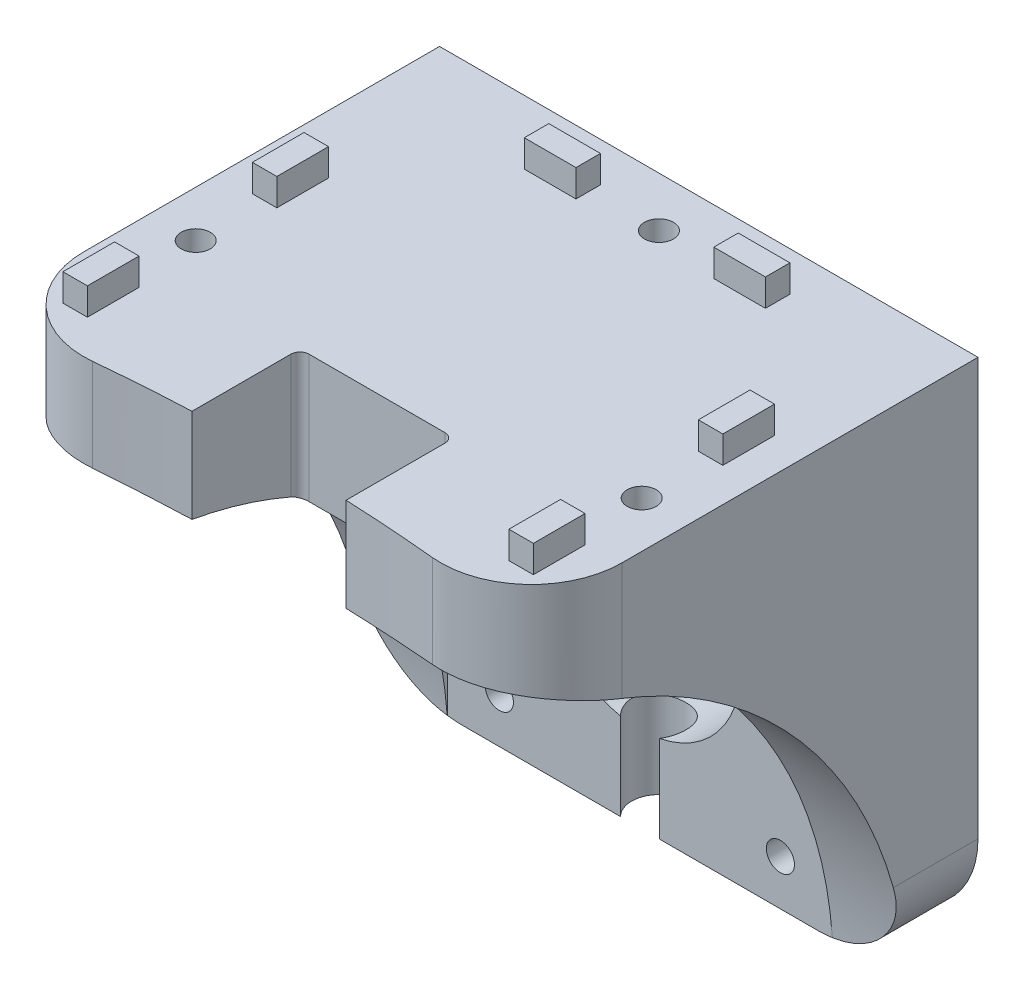
SolidWorks part; units mm, degrees
ref_plane "Alzado" through (0, 0, 0) normal (0, 0, 1) x (1, 0, 0)
ref_plane "Planta" through (0, 0, 0) normal (0, 1, 0) x (1, 0, 0)
ref_plane "Vista lateral" through (0, 0, 0) normal (1, 0, 0) x (0, 0, -1)
sketch "Croquis1" plane through (0, 0, 0) normal (0, 1, 0) x (1, 0, 0)
  line L1 (0, 0) -> (59.4, 0)
  line L2 (0, 0) -> (0, 48.6)
  line L3 (0, 48.6) -> (59.4, 48.6)
  line L4 (59.4, 0) -> (59.4, 48.6)
  dimension "D1" = 59.4
  dimension "D2" = 48.6
extrude "Saliente-Extruir1" add sketch "Croquis1" along normal blind 56
sketch "Croquis2" plane through (0, 56, 0) normal (0, 1, 0) x (1, 0, 0)
  line L1 (5.1, 48.6) -> (5.1, 0) construction
  line L2 (59.4, 48.6) -> (0, 48.6) construction
  line L3 (0, 0) -> (59.4, 0) construction
  line L4 (0, 45.1) -> (59.4, 45.1) construction
  line L5 (0, 48.6) -> (0, 0) construction
  line L6 (59.4, 0) -> (59.4, 48.6) construction
  line L7 (29.7, 48.6) -> (29.7, 0) construction
  line L8 (43.1, 46.35) -> (43.1, 43.45)
  line L9 (22.2, 46.35) -> (16.3, 46.35)
  line L10 (22.2, 46.35) -> (22.2, 43.45)
  line L11 (22.2, 43.45) -> (16.3, 43.45)
  line L12 (16.3, 46.35) -> (16.3, 43.45)
  line L13 (37.2, 43.45) -> (43.1, 43.45)
  line L14 (37.2, 46.35) -> (37.2, 43.45)
  line L15 (37.2, 46.35) -> (43.1, 46.35)
  line L16 (0, 18.6) -> (59.4, 18.6) construction
  line L17 (3.65, 26.1) -> (6.55, 26.1)
  line L18 (3.65, 26.1) -> (3.65, 32)
  line L19 (3.65, 32) -> (6.55, 32)
  line L20 (6.55, 26.1) -> (6.55, 32)
  line L21 (3.65, 11.1) -> (6.55, 11.1)
  line L22 (3.65, 11.1) -> (3.65, 5.2)
  line L23 (3.65, 5.2) -> (6.55, 5.2)
  line L24 (6.55, 11.1) -> (6.55, 5.2)
  line L25 (55.75, 5.2) -> (52.85, 5.2)
  line L26 (55.75, 11.1) -> (55.75, 5.2)
  line L27 (55.75, 11.1) -> (52.85, 11.1)
  line L28 (52.85, 11.1) -> (52.85, 5.2)
  line L29 (55.75, 26.1) -> (52.85, 26.1)
  line L30 (55.75, 26.1) -> (55.75, 32)
  line L31 (52.85, 26.1) -> (52.85, 32)
  line L32 (55.75, 32) -> (52.85, 32)
  circle A0 centre (29.7, 45.1) radius 1.575
  circle A1 centre (5.1, 18.6) radius 1.575
  circle A2 centre (54.3, 18.6) radius 1.575
  dimension "D3" = 3.15
  dimension "D7" = 7.5
  dimension "D8" = 26.5
  dimension "D1" = 5.1
  dimension "D2" = 3.5
  dimension "D4" = 5.9
  dimension "D5" = 2.9
  dimension "D6" = 1.25
  dimension "D9" = 5.9
  dimension "D10" = 2.9
  dimension "D11" = 1.45
  dimension "D12" = 7.5
extrude "Saliente-Extruir2" add sketch "Croquis2" along normal blind 3 contours L8 L13 L14 L15 | L10 L9 L12 L11 | L18 L17 L20 L19 | L29 L31 L32 L30 | L25 L28 L27 L26 | L21 L24 L23 L22
sketch "Croquis3" plane through (0, 56, 0) normal (0, 1, 0) x (1, 0, 0)
  line L0 (5.1, 26.1) -> (5.1, 11.1) construction
  line L1 (3.65, 26.1) -> (6.55, 26.1) construction
  line L2 (3.65, 11.1) -> (6.55, 11.1) construction
  line L6 (29.7, 48.6) -> (29.7, 0) construction
  line L7 (59.4, 48.6) -> (0, 48.6) construction
  line L8 (0, 0) -> (59.4, 0) construction
  line L10 (22.2, 46.35) -> (22.2, 43.45) construction
  circle A0 centre (29.7, 45.1) radius 1.6
  circle A1 centre (5.1, 18.6) radius 1.6
  circle A2 centre (54.3, 18.6) radius 1.6
  dimension "D1" = 3.2
  dimension "D2" = 3.5
  dimension "D3" = 7.5
extrude "Cortar-Extruir1" cut sketch "Croquis3" against normal up to surface (56 mm away) up to face at (29.7, 0, -24.3)
sketch "Croquis4" plane through (0, 0, -48.6) normal (0, 0, -1) x (-1, 0, 0)
  line L0 (-59.4, 56) -> (0, 56) construction
  line L1 (-59.4, 20.5) -> (0, 20.5) construction
  line L2 (-59.4, 56) -> (-59.4, 0) construction
  line L3 (-29.7, 0) -> (-29.7, 56) construction
  line L4 (-59.4, 0) -> (0, 0) construction
  line L5 (0, 56) -> (0, 0) construction
  circle A0 centre (-29.7, 20.5) radius 11.1
  circle A1 centre (-45.2, 36) radius 1.55
  circle A2 centre (-14.2, 36) radius 1.55
  circle A3 centre (-45.2, 5) radius 1.55
  circle A4 centre (-14.2, 5) radius 1.55
  dimension "D1" = 22.2
  dimension "D4" = 15.5
  dimension "D3" = 3.1
  dimension "D2" = 35.5
  dimension "D5" = 15.5
  dimension "D6" = 31
  dimension "D7" = 31
extrude "Cortar-Extruir2" cut sketch "Croquis4" against normal up to surface (48.6 mm away) up to face at (29.7, 28, 0)
sketch "Croquis5" plane through (0, 0, 0) normal (0, 0, 1) x (1, 0, 0)
  line L1 (50.95, 41.75) -> (8.45, 41.75)
  line L2 (50.95, 41.75) -> (50.95, -0.75)
  line L3 (50.95, -0.75) -> (8.45, -0.75)
  line L4 (8.45, 41.75) -> (8.45, -0.75)
  line L5 (50.95, 41.75) -> (8.45, -0.75) construction
  line L6 (50.95, -0.75) -> (8.45, 41.75) construction
  point P0 (29.7, 20.5)
  dimension "D1" = 42.5
  dimension "D2" = 42.5
extrude "Cortar-Extruir3" cut sketch "Croquis5" against normal blind 43
sketch "Croquis7" plane through (0, 0, 0) normal (0, 1, 0) x (1, 0, 0)
  circle A0 centre (29.7, 45.1) radius 3
  circle A1 centre (5.1, 18.6) radius 3
  circle A2 centre (54.3, 18.6) radius 3
  dimension "D1" = 6
extrude "Cortar-Extruir4" cut sketch "Croquis7" along normal blind 50
sketch "Croquis8" plane through (59.4, 0, 0) normal (1, 0, 0) x (0, 0, -1)
  line L0 (0, 0) -> (48.6, 0) construction
  line L1 (0, 56) -> (0, 0) construction
  line L2 (48.6, 56) -> (48.6, 0) construction
  line L3 (11.1, 56) -> (5.2, 56) construction
  line L4 (43, 0) -> (0, 0)
  line L5 (0, 0) -> (0, 46)
  arc A0 (43, 0) -> (0, 46) centre (-6.8756, -3.525) ccw
  dimension "D3" = 50
  dimension "D1" = 5.6
  dimension "D2" = 10
extrude "Cortar-Extruir5" cut sketch "Croquis8" against normal up to surface (59.4 mm away) up to face at (0, 28, -24.3)
sketch "Croquis9" plane through (0, 56, 0) normal (0, 1, 0) x (1, 0, 0)
  line L0 (0, 0) -> (59.4, 0) construction
  line L1 (0, 0) -> (59.4, 0)
  line L2 (0, 48.6) -> (0, 0) construction
  line L4 (21.2, 2.0897) -> (21.2, 14)
  line L5 (21.2, 14) -> (38.2, 14)
  line L6 (38.2, 2.0897) -> (38.2, 14)
  arc A0 (0, 0) -> (21.2, 2.0897) centre (29.7, -192.725) cw
  arc A1 (38.2, 2.0897) -> (59.4, 0) centre (29.7, -192.725) cw
  dimension "D1" = 195
  dimension "D2" = 17
  dimension "D4" = 21.2
  dimension "D5" = 14
extrude "Cortar-Extruir6" cut sketch "Croquis9" against normal through all
sketch "Croquis10" plane through (0, 0, -48.6) normal (0, 0, -1) x (-1, 0, 0)
  line L4 (-59.4, 0) -> (0, 0)
  line L5 (0, 0) -> (0, 56)
  line L6 (0, 56) -> (-59.4, 56)
  line L7 (-59.4, 56) -> (-59.4, 0)
  line L8 (-59.4, 0) -> (0, 0)
  line L9 (0, 0) -> (0, 56)
  line L10 (0, 56) -> (-59.4, 56)
  line L11 (-59.4, 56) -> (-59.4, 0)
  circle A0 centre (-14.2, 36) radius 1.55 construction
  circle A1 centre (-45.2, 36) radius 1.55 construction
  circle A2 centre (-45.2, 5) radius 1.55 construction
  circle A3 centre (-29.7, 20.5) radius 11.1 construction
  circle A4 centre (-14.2, 5) radius 1.55 construction
  circle A5 centre (-14.2, 36) radius 1.55
  circle A6 centre (-45.2, 36) radius 1.55
  circle A7 centre (-45.2, 5) radius 1.55
  circle A8 centre (-29.7, 20.5) radius 11.1
  circle A9 centre (-14.2, 5) radius 1.55
  dimension "D1" = 0
extrude "Saliente-Extruir3" add sketch "Croquis10" along normal blind 2
fillet "Redondeo1" radius 10 2 edges at (59.4, 0, -46.8) (0, 0, -46.8)
fillet "Redondeo2" radius 10 2 edges at (0, 51, 0) (59.4, 51, 0)
fillet "Redondeo3" radius 1 2 edges at (21.2, 48.9543, -14) (38.2, 48.9543, -14)
sketch "Croquis11" plane through (0, 0, -50.6) normal (0, 0, -1) x (-1, 0, 0)
  circle A0 centre (-45.2, 36) radius 3.25
  circle A1 centre (-14.2, 36) radius 3.25
  circle A2 centre (-14.2, 5) radius 3.25
  circle A3 centre (-45.2, 5) radius 3.25
  dimension "D1" = 6.5
extrude "Cortar-Extruir7" cut sketch "Croquis11" against normal blind 3.5
fillet "Redondeo4" radius 1 4 edges at (41.95, 36, -47.1) (41.95, 5, -47.1) (10.95, 5, -47.1) (10.95, 36, -47.1)
sketch "Croquis12" plane through (0, 59, 0) normal (0, 1, 0) x (1, 0, 0)
  line L0 (16.4, 43.55) -> (22.1, 43.55)
  line L1 (22.1, 43.55) -> (22.1, 46.25)
  line L2 (22.1, 46.25) -> (16.4, 46.25)
  line L3 (16.4, 46.25) -> (16.4, 43.55)
  line L4 (16.3, 43.45) -> (22.2, 43.45)
  line L5 (22.2, 43.45) -> (22.2, 46.35)
  line L6 (22.2, 46.35) -> (16.3, 46.35)
  line L7 (16.3, 46.35) -> (16.3, 43.45)
  line L8 (16.3, 43.45) -> (22.2, 43.45)
  line L9 (22.2, 43.45) -> (22.2, 46.35)
  line L10 (22.2, 46.35) -> (16.3, 46.35)
  line L11 (16.3, 46.35) -> (16.3, 43.45)
  line L12 (43.1, 46.35) -> (37.2, 46.35)
  line L13 (37.2, 46.35) -> (37.2, 43.45)
  line L14 (37.2, 43.45) -> (43.1, 43.45)
  line L15 (43.1, 43.45) -> (43.1, 46.35)
  line L16 (43.1, 46.35) -> (37.2, 46.35)
  line L17 (37.2, 46.35) -> (37.2, 43.45)
  line L18 (37.2, 43.45) -> (43.1, 43.45)
  line L19 (43.1, 43.45) -> (43.1, 46.35)
  line L20 (55.75, 26.1) -> (55.75, 32)
  line L21 (55.75, 32) -> (52.85, 32)
  line L22 (52.85, 32) -> (52.85, 26.1)
  line L23 (52.85, 26.1) -> (55.75, 26.1)
  line L24 (55.75, 26.1) -> (55.75, 32)
  line L25 (55.75, 32) -> (52.85, 32)
  line L26 (52.85, 32) -> (52.85, 26.1)
  line L27 (52.85, 26.1) -> (55.75, 26.1)
  line L28 (55.75, 5.2) -> (55.75, 11.1)
  line L29 (55.75, 11.1) -> (52.85, 11.1)
  line L30 (52.85, 11.1) -> (52.85, 5.2)
  line L31 (52.85, 5.2) -> (55.75, 5.2)
  line L32 (55.75, 5.2) -> (55.75, 11.1)
  line L33 (55.75, 11.1) -> (52.85, 11.1)
  line L34 (52.85, 11.1) -> (52.85, 5.2)
  line L35 (52.85, 5.2) -> (55.75, 5.2)
  line L36 (3.65, 11.1) -> (3.65, 5.2)
  line L37 (3.65, 5.2) -> (6.55, 5.2)
  line L38 (6.55, 5.2) -> (6.55, 11.1)
  line L39 (6.55, 11.1) -> (3.65, 11.1)
  line L40 (3.65, 11.1) -> (3.65, 5.2)
  line L41 (3.65, 5.2) -> (6.55, 5.2)
  line L42 (6.55, 5.2) -> (6.55, 11.1)
  line L43 (6.55, 11.1) -> (3.65, 11.1)
  line L44 (6.55, 32) -> (3.65, 32)
  line L45 (3.65, 32) -> (3.65, 26.1)
  line L46 (3.65, 26.1) -> (6.55, 26.1)
  line L47 (6.55, 26.1) -> (6.55, 32)
  line L48 (6.55, 32) -> (3.65, 32)
  line L49 (3.65, 32) -> (3.65, 26.1)
  line L50 (3.65, 26.1) -> (6.55, 26.1)
  line L51 (6.55, 26.1) -> (6.55, 32)
  line L52 (43, 46.25) -> (37.3, 46.25)
  line L53 (37.3, 46.25) -> (37.3, 43.55)
  line L54 (37.3, 43.55) -> (43, 43.55)
  line L55 (43, 43.55) -> (43, 46.25)
  line L56 (55.65, 26.2) -> (55.65, 31.9)
  line L57 (55.65, 31.9) -> (52.95, 31.9)
  line L58 (52.95, 31.9) -> (52.95, 26.2)
  line L59 (52.95, 26.2) -> (55.65, 26.2)
  line L60 (55.65, 5.3) -> (55.65, 11)
  line L61 (55.65, 11) -> (52.95, 11)
  line L62 (52.95, 11) -> (52.95, 5.3)
  line L63 (52.95, 5.3) -> (55.65, 5.3)
  line L64 (6.45, 31.9) -> (3.75, 31.9)
  line L65 (3.75, 31.9) -> (3.75, 26.2)
  line L66 (3.75, 26.2) -> (6.45, 26.2)
  line L67 (6.45, 26.2) -> (6.45, 31.9)
  line L68 (3.75, 11) -> (3.75, 5.3)
  line L69 (3.75, 5.3) -> (6.45, 5.3)
  line L70 (6.45, 5.3) -> (6.45, 11)
  line L71 (6.45, 11) -> (3.75, 11)
  dimension "D1" = 0
  dimension "D2" = 0
  dimension "D3" = 0
  dimension "D4" = 0
  dimension "D5" = 0
  dimension "D6" = 0
  dimension "D7" = 0.1
  dimension "D8" = 0.1
  dimension "D9" = 0.1
  dimension "D10" = 0.1
  dimension "D11" = 0.1
  dimension "D12" = 0.1
extrude "Cortar-Extruir9" cut sketch "Croquis12" against normal up to surface (3 mm away) up to face at (29.7, 56, -43.5)
fillet "Redondeo5" radius 0.5 4 edges at (10.95, 5, -50.6) (10.95, 36, -50.6) (41.95, 36, -50.6) (41.95, 5, -50.6)
